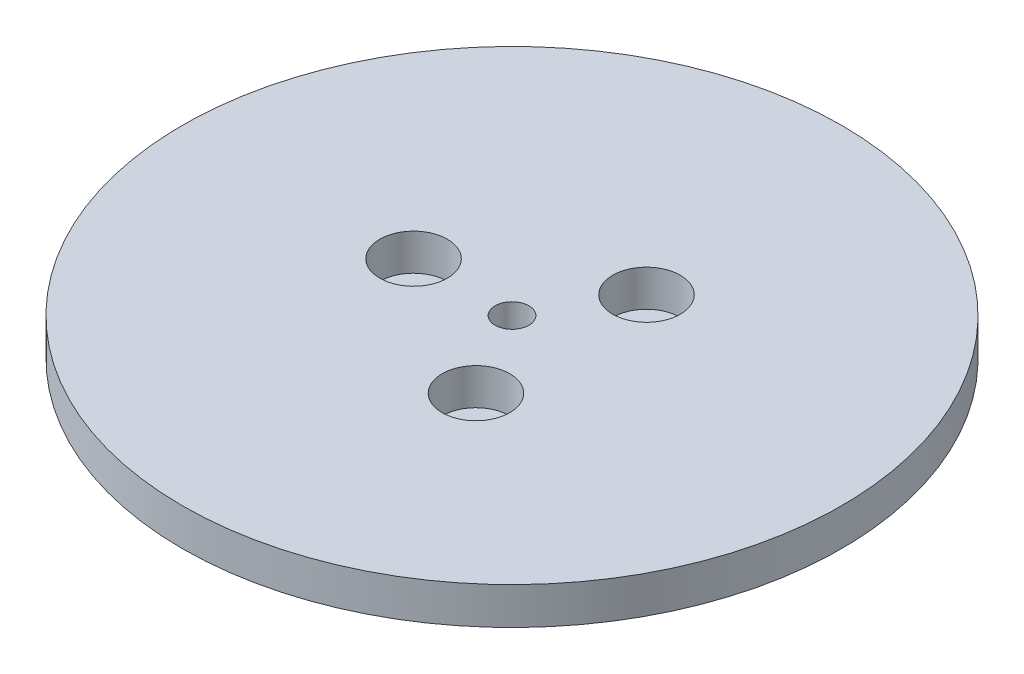
SolidWorks part; units mm, degrees
ref_plane "Front Plane" through (0, 0, 0) normal (0, 0, 1) x (1, 0, 0)
ref_plane "Top Plane" through (0, 0, 0) normal (0, 1, 0) x (1, 0, 0)
ref_plane "Right Plane" through (0, 0, 0) normal (1, 0, 0) x (0, 0, -1)
sketch "Sketch1" plane through (0, 0, 0) normal (0, 1, 0) x (1, 0, 0)
  circle A0 centre (0, 0) radius 97.5
  dimension "FLANGE_OD" = 195
extrude "Boss-Extrude1" add sketch "Sketch1" along normal blind 11
sketch "Sketch2" plane through (0, 0, 0) normal (0, 1, 0) x (1, 0, 0)
  circle A0 centre (0, 0) radius 5
  dimension "BORE_D" = 10
extrude "Cut-Extrude1" cut sketch "Sketch2" along normal through all
sketch "Sketch3" plane through (0, 11, 0) normal (0, 1, 0) x (1, 0, 0)
  circle A0 centre (0, 0) radius 29.1281 construction
  circle A1 centre (-29.1281, 0) radius 10
  dimension "BOLT_D" = 20
  dimension "BOLT_PCD" = 58.2562
extrude "Cut-Extrude2" cut sketch "Sketch3" against normal blind 10.7901
pattern_circular "CirPattern1" count 3 over 360 about axis through (0, 0, 0) along (0, 1, 0) of "Cut-Extrude2"
